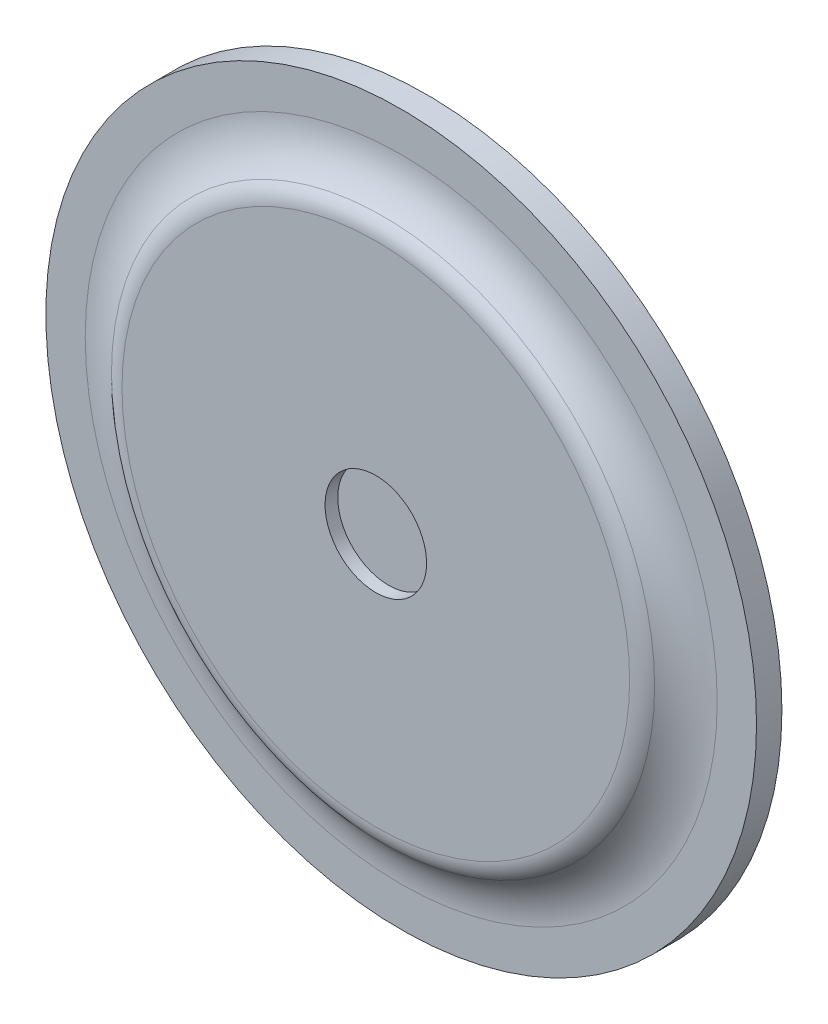
SolidWorks part; units mm, degrees
ref_plane "Front Plane" through (0, 0, 0) normal (0, 0, 1) x (1, 0, 0)
ref_plane "Top Plane" through (0, 0, 0) normal (0, 1, 0) x (1, 0, 0)
ref_plane "Right Plane" through (0, 0, 0) normal (1, 0, 0) x (0, 0, -1)
sketch "Sketch1" plane through (0, 0, 0) normal (1, 0, 0) x (0, 0, -1)
  line L1 (-21.59, 26.9875) -> (-21.59, 0)
  line L2 (0, 0) -> (87.2706, 0) construction
  line L6 (-31.75, 31.75) -> (-31.75, 0)
  line L7 (-31.75, 0) -> (-21.59, 0)
  line L8 (-25.4, 31.75) -> (-25.4, 26.9875)
  line L9 (-25.4, 26.9875) -> (-21.59, 26.9875)
  line L10 (-28.575, 39.5271) -> (-28.575, 44.45)
  line L11 (-28.575, 44.45) -> (-25.4, 44.45)
  line L12 (-25.4, 44.45) -> (-25.4, 31.75)
  line L13 (49.6911, 31.75) -> (-25.4, 31.75) construction
  arc A1 (-28.575, 39.5271) -> (-30.8429, 33.972) centre (-36.5125, 39.5271) cw
  arc A2 (-31.75, 31.75) -> (-30.8429, 33.972) centre (-28.575, 31.75) cw
  point P10 (0, 0)
  point P11 (0, 0)
  point P12 (-31.75, 31.75)
  point P21 (0, 0)
  point P22 (0, 0)
  point P23 (0, 0)
  point P24 (0, 0)
  point P25 (0, 0)
  point P26 (0, 0)
  point P27 (0, 0)
  dimension "D3" = 12.7
  dimension "D5" = 3.175
  dimension "D7" = 7.9375
  dimension "D1" = 6.35
  dimension "D2" = 10.16
  dimension "D4" = 3.175
  dimension "D6" = 6.35
revolve "Revolve1" add sketch "Sketch1" angle 360 about L7 region at (0, 18.2305, 26.9575)
sketch "Sketch2" plane through (0, 0, 0) normal (1, 0, 0) x (0, 0, -1)
  line L3 (-25.4, 26.9875) -> (-21.59, 26.9875) construction
  line L4 (-31.75, 31.75) -> (-31.75, 0) construction
  line L5 (-21.59, 26.9875) -> (-21.59, 0) construction
  line L6 (-21.59, 26.9875) -> (-21.59, 0) construction
  line L7 (-30.1625, 25.4) -> (-23.1775, 25.4)
  line L8 (-30.1625, 31.75) -> (-30.1625, 0)
  line L9 (-30.1625, 25.4) -> (-30.1625, 6.35)
  line L10 (-23.1775, 25.4) -> (-23.1775, 0)
  line L11 (-31.75, 0) -> (-23.1775, 0)
  line L12 (-31.7498, 25.4) -> (-23.1775, 25.4) construction
  line L13 (-30.1625, 6.35) -> (-31.75, 6.35)
  line L15 (0, 0) -> (87.2706, 0) construction
  line L16 (-31.75, 6.35) -> (-31.75, 0)
  line L18 (-31.7498, 26.9875) -> (-21.59, 26.9875) construction
  point P19 (0, 0)
  dimension "D3" = 6.35
  dimension "D4" = 1.5875
  dimension "D1" = 1.5875
  dimension "D2" = 1.5875
revolve "Cut-Revolve1" cut sketch "Sketch2" angle 360 about L11
sketch "Sketch3" plane through (0, 0, 21.59) normal (0, 0, -1) x (-1, 0, 0)
  line L0 (0, 31.75) -> (0, 0) construction
  circle A0 centre (0, 3.175) radius 0.7938
  circle A1 centre (2.7496, 1.5875) radius 0.7938
  circle A2 centre (2.7496, -1.5875) radius 0.7938
  circle A3 centre (0, -3.175) radius 0.7937
  circle A4 centre (-2.7496, -1.5875) radius 0.7938
  circle A5 centre (-2.7496, 1.5875) radius 0.7938
  point P6 (-0.4034, -4.6773)
  point P7 (0, 0)
  point P17 (0, 0)
  dimension "D1" = 1.5875
  dimension "D2" = 3.175
  dimension "D3" = 6
extrude "Cut-Extrude1" cut sketch "Sketch3" against normal up to surface (1.5875 mm away) up to face at (0, -25.4, 23.1775)
chamfer "Chamfer1" distance 0.1984 angle 45 13 edges at (-2.7496, -2.3812, 23.1775) (-2.7496, 0.7938, 23.1775) (0, -3.9688, 23.1775) (2.7496, -2.3813, 23.1775) (0, 2.3812, 23.1775) (2.7496, 0.7937, 23.1775) (-3.5434, -1.5875, 21.59) (-3.5434, 1.5875, 21.59) (-0.7938, -3.175, 21.59) (-0.7937, 3.175, 21.59) (1.9559, 1.5875, 21.59) (1.9559, -1.5875, 21.59) (26.9875, 0, 21.59)
